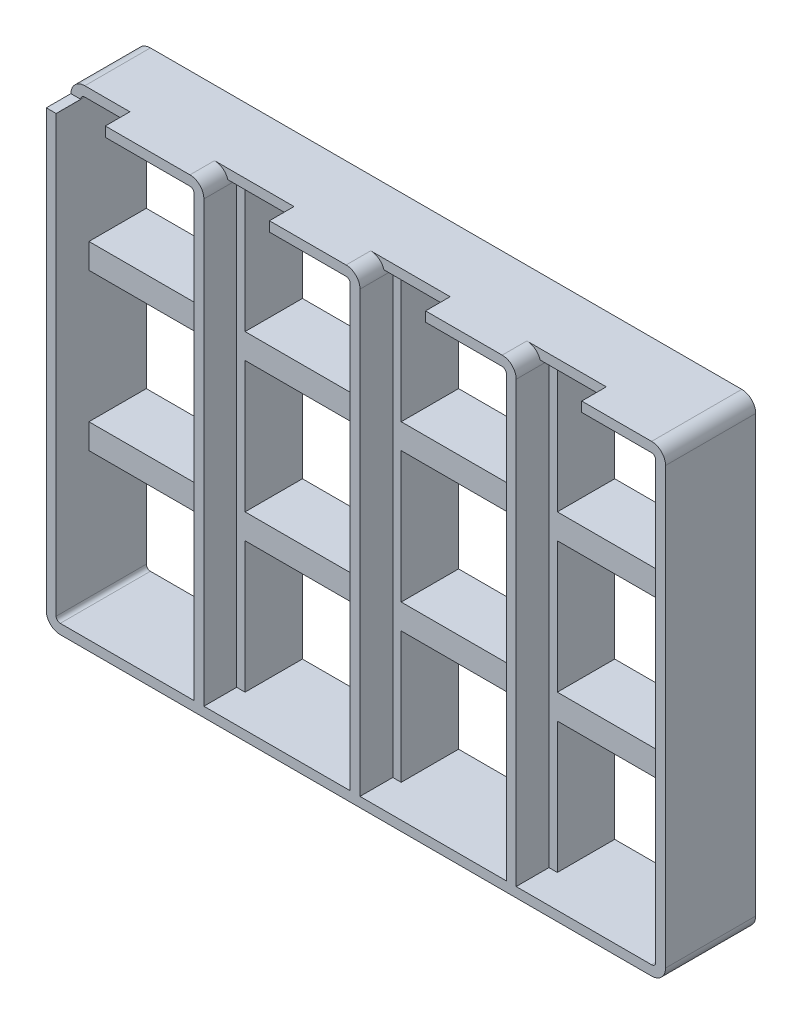
SolidWorks part; units mm, degrees
ref_plane "Front Plane" through (0, 0, 0) normal (0, 0, 1) x (1, 0, 0)
ref_plane "Top Plane" through (0, 0, 0) normal (0, 1, 0) x (1, 0, 0)
ref_plane "Right Plane" through (0, 0, 0) normal (1, 0, 0) x (0, 0, -1)
sketch "Skica1" plane through (0, 0, 0) normal (0, 0, 1) x (1, 0, 0)
  line L0 (11.05, 8) -> (11.05, -8)
  line L1 (-8, 8) -> (8, 8)
  line L2 (-8, 8) -> (-8, -7.5)
  line L3 (-7.5, -8) -> (8, -8)
  line L4 (8, 8) -> (8, -8)
  line L5 (-8, 8) -> (8, -8) construction
  line L6 (-8, -8) -> (8, 8) construction
  line L7 (11.05, 8) -> (27.05, 8)
  line L8 (27.05, 8) -> (27.05, -8)
  line L9 (11.05, -8) -> (27.05, -8)
  line L10 (30.1, 8) -> (30.1, -8)
  line L11 (30.1, 8) -> (46.1, 8)
  line L12 (46.1, 8) -> (46.1, -8)
  line L13 (30.1, -8) -> (46.1, -8)
  line L14 (49.15, 8) -> (49.15, -8)
  line L15 (49.15, 8) -> (65.15, 8)
  line L16 (65.15, 8) -> (65.15, -7.5)
  line L17 (49.15, -8) -> (64.65, -8)
  line L18 (11.05, 27.05) -> (11.05, 11.05)
  line L19 (11.05, 27.05) -> (27.05, 27.05)
  line L20 (27.05, 27.05) -> (27.05, 11.05)
  line L21 (11.05, 11.05) -> (27.05, 11.05)
  line L22 (30.1, 27.05) -> (30.1, 11.05)
  line L23 (30.1, 27.05) -> (46.1, 27.05)
  line L24 (46.1, 27.05) -> (46.1, 11.05)
  line L25 (30.1, 11.05) -> (46.1, 11.05)
  line L26 (49.15, 27.05) -> (49.15, 11.05)
  line L27 (49.15, 27.05) -> (65.15, 27.05)
  line L28 (65.15, 27.05) -> (65.15, 11.05)
  line L29 (49.15, 11.05) -> (65.15, 11.05)
  line L30 (11.05, 46.1) -> (11.05, 30.1)
  line L31 (11.05, 46.1) -> (27.05, 46.1)
  line L32 (27.05, 46.1) -> (27.05, 30.1)
  line L33 (11.05, 30.1) -> (27.05, 30.1)
  line L34 (30.1, 46.1) -> (30.1, 30.1)
  line L35 (30.1, 46.1) -> (46.1, 46.1)
  line L36 (46.1, 46.1) -> (46.1, 30.1)
  line L37 (30.1, 30.1) -> (46.1, 30.1)
  line L38 (49.15, 46.1) -> (49.15, 30.1)
  line L39 (49.15, 46.1) -> (64.65, 46.1)
  line L40 (65.15, 45.6) -> (65.15, 30.1)
  line L41 (49.15, 30.1) -> (65.15, 30.1)
  line L42 (-8, 27.05) -> (-8, 11.05)
  line L43 (-8, 27.05) -> (8, 27.05)
  line L44 (8, 27.05) -> (8, 11.05)
  line L45 (-8, 11.05) -> (8, 11.05)
  line L46 (-8, 45.6) -> (-8, 30.1)
  line L47 (-7.5, 46.1) -> (8, 46.1)
  line L48 (8, 46.1) -> (8, 30.1)
  line L49 (-8, 30.1) -> (8, 30.1)
  line L51 (-7.5, 47.3) -> (64.65, 47.3)
  line L52 (-9.2, 45.6) -> (-9.2, -7.5)
  line L53 (-7.5, -9.2) -> (64.65, -9.2)
  line L54 (66.35, 45.6) -> (66.35, -7.5)
  arc A0 (-8, -7.5) -> (-7.5, -8) centre (-7.5, -7.5) ccw
  arc A1 (65.15, -7.5) -> (64.65, -8) centre (64.65, -7.5) cw
  arc A2 (64.65, 46.1) -> (65.15, 45.6) centre (64.65, 45.6) cw
  arc A3 (-8, 45.6) -> (-7.5, 46.1) centre (-7.5, 45.6) cw
  arc A4 (-9.2, -7.5) -> (-7.5, -9.2) centre (-7.5, -7.5) ccw
  arc A5 (64.65, -9.2) -> (66.35, -7.5) centre (64.65, -7.5) ccw
  arc A6 (64.65, 47.3) -> (66.35, 45.6) centre (64.65, 45.6) cw
  arc A7 (-7.5, 47.3) -> (-9.2, 45.6) centre (-7.5, 45.6) ccw
  point P0 (0, 0)
  point P65 (-9.2, -9.2)
  point P68 (66.35, -9.2)
  point P73 (-9.2, 47.3)
  dimension "D9" = 0.5
  dimension "D10" = 1.7
  dimension "D1" = 16
  dimension "D2" = 16
  dimension "D5" = 1.2
  dimension "D6" = 1.2
  dimension "D7" = 1.2
  dimension "D8" = 1.2
  dimension "D11" = 19.05
  dimension "D12" = 19.05
  dimension "D13" = 1.2
  dimension "D3" = 4
  dimension "D4" = 3
extrude "Přidat vysunutím1" add sketch "Skica1" along normal blind 7
sketch "Skica2" plane through (0, 0, 7) normal (0, 0, 1) x (1, 0, 0)
  line L0 (64.65, 46.1) -> (48.125, 46.1)
  line L1 (-8, 45.6) -> (-8, -7.5)
  line L2 (-7.5, -8) -> (8.825, -8)
  line L3 (65.15, -7.5) -> (65.15, 45.6)
  line L4 (-7.5, -9.2) -> (64.65, -9.2)
  line L5 (66.35, -7.5) -> (66.35, 45.6)
  line L6 (64.65, 47.3) -> (-7.5, 47.3)
  line L7 (-9.2, 45.6) -> (-9.2, -7.5)
  line L8 (-7.5, -9.2) -> (64.65, -9.2)
  line L9 (66.35, -7.5) -> (66.35, 45.6)
  line L10 (64.65, 47.3) -> (-7.5, 47.3)
  line L11 (-9.2, 45.6) -> (-9.2, -7.5)
  line L12 (48.125, -8) -> (64.65, -8)
  line L14 (8.825, 46.1) -> (8.825, -8)
  line L16 (10.025, 46.1) -> (10.025, -8)
  line L18 (27.875, 46.1) -> (27.875, -8)
  line L20 (29.075, 46.1) -> (29.075, -8)
  line L22 (46.925, 46.1) -> (46.925, -8)
  line L24 (48.125, 46.1) -> (48.125, -8)
  line L25 (-7.5, -8) -> (64.65, -8) construction
  line L26 (8, 30.1) -> (8, 46.1) construction
  line L27 (27.05, 30.1) -> (27.05, 46.1) construction
  line L28 (46.1, 30.1) -> (46.1, 46.1) construction
  line L29 (8.825, 46.1) -> (-7.5, 46.1)
  line L30 (64.65, 46.1) -> (-7.5, 46.1) construction
  line L31 (27.875, 46.1) -> (10.025, 46.1)
  line L32 (46.925, 46.1) -> (29.075, 46.1)
  line L33 (29.075, -8) -> (46.925, -8)
  line L34 (10.025, -8) -> (27.875, -8)
  arc A0 (-7.5, 46.1) -> (-8, 45.6) centre (-7.5, 45.6) ccw
  arc A1 (-8, -7.5) -> (-7.5, -8) centre (-7.5, -7.5) ccw
  arc A2 (64.65, -8) -> (65.15, -7.5) centre (64.65, -7.5) ccw
  arc A3 (65.15, 45.6) -> (64.65, 46.1) centre (64.65, 45.6) ccw
  arc A4 (-9.2, -7.5) -> (-7.5, -9.2) centre (-7.5, -7.5) ccw
  arc A5 (64.65, -9.2) -> (66.35, -7.5) centre (64.65, -7.5) ccw
  arc A6 (66.35, 45.6) -> (64.65, 47.3) centre (64.65, 45.6) ccw
  arc A7 (-7.5, 47.3) -> (-9.2, 45.6) centre (-7.5, 45.6) ccw
  arc A8 (-9.2, -7.5) -> (-7.5, -9.2) centre (-7.5, -7.5) ccw
  arc A9 (64.65, -9.2) -> (66.35, -7.5) centre (64.65, -7.5) ccw
  arc A10 (66.35, 45.6) -> (64.65, 47.3) centre (64.65, 45.6) ccw
  arc A11 (-7.5, 47.3) -> (-9.2, 45.6) centre (-7.5, 45.6) ccw
  dimension "D3" = 1.2
  dimension "D4" = 1.2
  dimension "D5" = 1.2
  dimension "D6" = 0.825
  dimension "D7" = 0.825
  dimension "D8" = 0.825
  dimension "D1" = 0
  dimension "D2" = 1.2
extrude "Přidat vysunutím2" add sketch "Skica2" along normal blind 4
sketch "Skica3" plane through (0, 0, 11) normal (0, 0, 1) x (1, 0, 0)
  line L0 (-8, 45.6) -> (-8, -7.5) construction
  line L1 (-9.8685, 48.6628) -> (-2, 48.6628)
  line L2 (-9.8685, 48.6628) -> (-9.8685, 45.6199)
  line L3 (-9.8685, 45.6199) -> (-2, 45.6199)
  line L4 (-2, 48.6628) -> (-2, 45.6199)
  line L5 (10.025, 46.1) -> (18.025, 46.1)
  line L6 (10.025, 46.1) -> (10.025, 48.3191)
  line L7 (10.025, 48.3191) -> (18.025, 48.3191)
  line L8 (18.025, 46.1) -> (18.025, 48.3191)
  line L9 (29.075, 46.1) -> (37.075, 46.1)
  line L10 (29.075, 46.1) -> (29.075, 48.8721)
  line L11 (29.075, 48.8721) -> (37.075, 48.8721)
  line L12 (37.075, 46.1) -> (37.075, 48.8721)
  line L13 (48.125, 46.1) -> (56.125, 46.1)
  line L14 (48.125, 46.1) -> (48.125, 48.6628)
  line L15 (48.125, 48.6628) -> (56.125, 48.6628)
  line L16 (56.125, 46.1) -> (56.125, 48.6628)
  dimension "D1" = 8
  dimension "D2" = 8
  dimension "D3" = 8
  dimension "D4" = 6
extrude "Odebrat vysunutím1" cut sketch "Skica3" against normal blind 3
fillet "Zaoblit1" radius 0.5 3 edges at (46.925, 46.1, 9) (27.875, 46.1, 9) (8.825, 46.1, 9)
fillet "Zaoblit2" radius 1.7 3 edges at (48.125, 47.3, 9.5) (29.075, 47.3, 9.5) (10.025, 47.3, 9.5)
